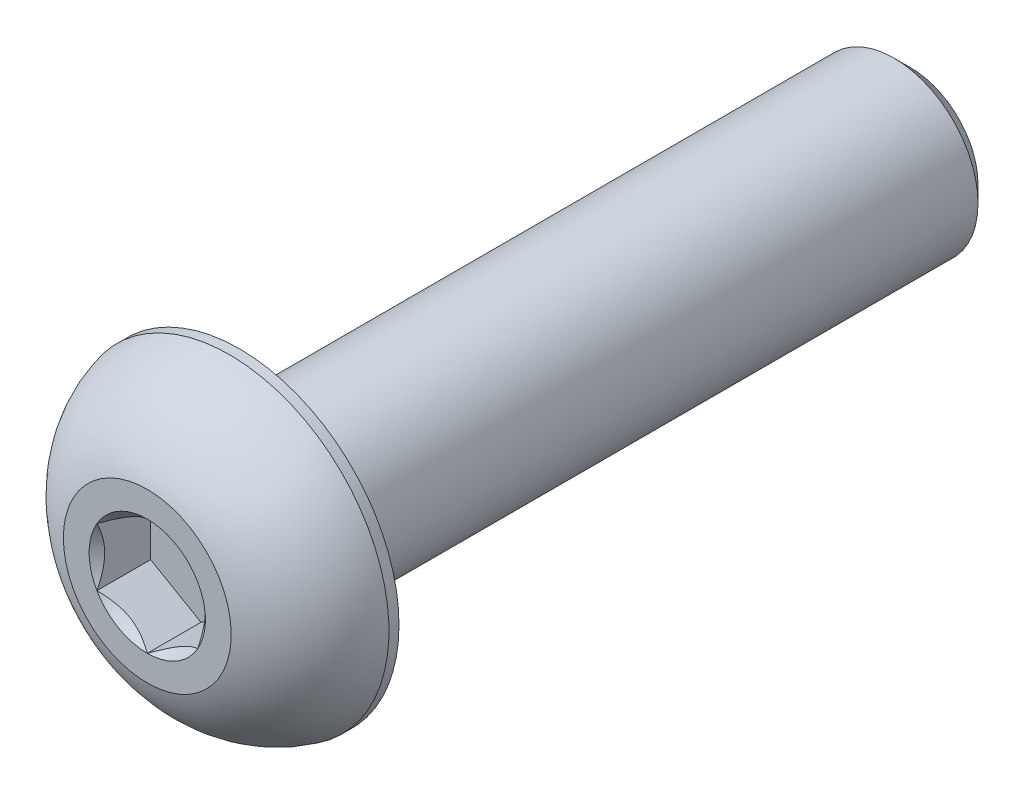
SolidWorks part; units mm, degrees
ref_plane "Front Plane" through (0, 0, 0) normal (0, 0, 1) x (1, 0, 0)
ref_plane "Top Plane" through (0, 0, 0) normal (0, 1, 0) x (1, 0, 0)
ref_plane "Right Plane" through (0, 0, 0) normal (1, 0, 0) x (0, 0, -1)
sketch "Sketch1" plane through (0, 0, 0) normal (0, 0, 1) x (1, 0, 0)
  circle A0 centre (-20, 0) radius 2.5
  dimension "D1" = 5
  dimension "D2" = 20
extrude "Boss-Extrude1" add sketch "Sketch1" against normal blind 20 from offset 21.2 offset against normal yes
sketch "Sketch2" plane through (0, 0, -21.2) normal (0, 0, 1) x (1, 0, 0)
  circle A0 centre (-20, 0) radius 4.75
  dimension "D1" = 9.5
extrude "Boss-Extrude2" add sketch "Sketch2" along normal blind 2.75
ref_plane "Plane1" through (-20, 0, 0) normal (1, 0, 0) x (0, 0, -1)
sketch "Sketch3" plane through (-20, 0, 0) normal (1, 0, 0) x (0, 0, -1)
  line L0 (21.2, 4.75) -> (18.45, 4.75) construction
  line L1 (18.45, 4.75) -> (18.45, -4.75) construction
  line L2 (18.45, 2.5) -> (17.45, 2.5)
  line L3 (17.45, 2.5) -> (17.45, 5.8)
  line L4 (17.45, 5.8) -> (20.9, 5.8)
  line L5 (20.9, 5.8) -> (20.9, 4.75)
  line L6 (21.2, -4.75) -> (21.2, 4.75) construction
  line L7 (41.2, 0) -> (18.45, 0) construction
  line L8 (41.2, -2.5) -> (41.2, 2.5) construction
  arc A0 (20.9, 4.75) -> (18.45, 2.5) centre (21.6808, 1.4409) ccw
  point P16 (17.95, 2.5)
  dimension "D5" = 3.4
  dimension "D1" = 0.3
  dimension "D2" = 1
  dimension "D3" = 2.5
  dimension "D4" = 3.3
revolve "Cut-Revolve1" cut sketch "Sketch3" angle 360 about L7
sketch "Sketch4" plane through (0, 0, -18.45) normal (0, 0, 1) x (1, 0, 0)
  line L1 (-20, 1.7321) -> (-21.5, 0.866)
  line L2 (-21.5, 0.866) -> (-21.5, -0.866)
  line L3 (-21.5, -0.866) -> (-20, -1.7321)
  line L4 (-20, -1.7321) -> (-18.5, -0.866)
  line L5 (-18.5, -0.866) -> (-18.5, 0.866)
  line L6 (-18.5, 0.866) -> (-20, 1.7321)
  circle A0 centre (-20, 0) radius 1.5 construction
  dimension "D1" = 3
extrude "Cut-Extrude1" cut sketch "Sketch4" against normal blind 1.6
sketch "Sketch5" plane through (0, 0, -18.45) normal (0, 0, 1) x (1, 0, 0)
  circle A0 centre (-20, 0) radius 1.7321
extrude "Cut-Extrude2" cut sketch "Sketch5" against normal blind 1 draft 45
chamfer "Chamfer1" distance 0.5 angle 45 1 edges at (-17.5, 0, -41.2)
